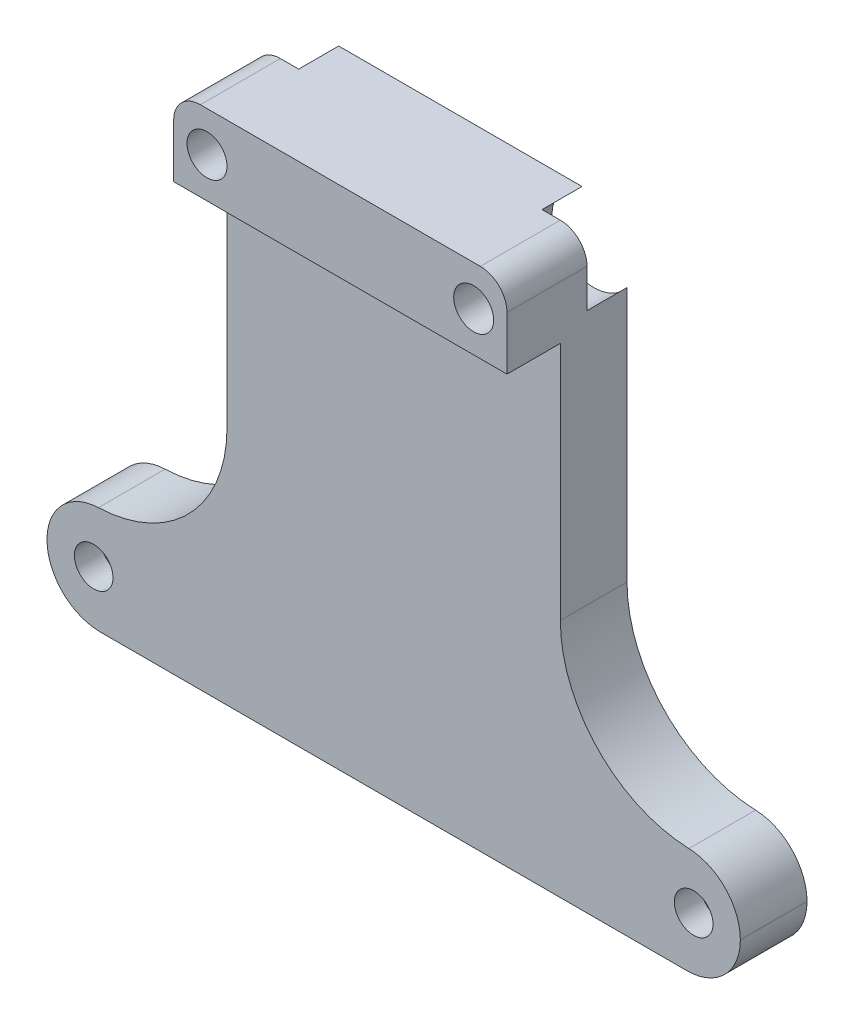
SolidWorks part; units mm, degrees
ref_plane "Спереди" through (0, 0, 0) normal (0, 0, 1) x (1, 0, 0)
ref_plane "Сверху" through (0, 0, 0) normal (0, 1, 0) x (1, 0, 0)
ref_plane "Справа" through (0, 0, 0) normal (1, 0, 0) x (0, 0, -1)
sketch "Эскиз1" plane through (0, 0, 0) normal (0, 0, 1) x (1, 0, 0)
  line L0 (-1000, 0) -> (49000, 0) construction
  line L1 (-26, -4) -> (26, -4)
  line L2 (-26, -4) -> (-26, 4)
  line L3 (-26, 4) -> (26, 4)
  line L4 (26, -4) -> (26, 4)
  line L5 (-26, -4) -> (26, 4) construction
  line L6 (-26, 4) -> (26, -4) construction
  circle A0 centre (-22.5, 0) radius 1.45
  circle A1 centre (22.5, 0) radius 1.45
  point P0 (0, 0)
  dimension "D2" = 2.9
  dimension "D1" = 8
  dimension "D3" = 45
  dimension "D4" = 22.5
  dimension "D5" = 52
extrude "Бобышка-Вытянуть1" add sketch "Эскиз1" along normal blind 5
sketch "Эскиз2" plane through (0, 0, 0) normal (0, 0, -1) x (-1, 0, 0)
  line L0 (-26, 4) -> (26, 4) construction
  line L1 (-12.5, 4) -> (12.5, 4)
  line L2 (-12.5, 4) -> (-12.5, 38)
  line L3 (-12.5, 38) -> (12.5, 38)
  line L4 (12.5, 4) -> (12.5, 38)
  line L5 (-12.5, 4) -> (12.5, 38) construction
  line L6 (-12.5, 38) -> (12.5, 4) construction
  line L7 (-1006.5256, 35) -> (48993.4744, 35) construction
  line L8 (0, -1000) -> (0, 49000) construction
  circle A0 centre (-10, 35) radius 1.5
  circle A1 centre (10, 35) radius 1.5
  point P4 (0, 21)
  dimension "D1" = 20
  dimension "D3" = 3
  dimension "D2" = 10
  dimension "D4" = 25
  dimension "D5" = 31
  dimension "D6" = 34
extrude "Бобышка-Вытянуть2" add sketch "Эскиз2" against normal blind 5
sketch "Эскиз3" plane through (0, 0, 5) normal (0, 0, -1) x (-1, 0, 0)
  line L0 (12.5, 4) -> (12.5, 38) construction
  line L1 (-12.5, 38) -> (12.5, 38)
  line L2 (-12.5, 38) -> (-12.5, 32)
  line L3 (-12.5, 32) -> (12.5, 32)
  line L4 (12.5, 38) -> (12.5, 32)
  line L5 (-12.5, 38) -> (12.5, 32) construction
  line L6 (-12.5, 32) -> (12.5, 38) construction
  circle A0 centre (10, 35) radius 1.5 construction
  circle A1 centre (-10, 35) radius 1.5 construction
  circle A2 centre (10, 35) radius 1.5
  circle A3 centre (-10, 35) radius 1.5
  point P4 (0, 35)
  dimension "D1" = 6
extrude "Бобышка-Вытянуть3" add sketch "Эскиз3" against normal blind 4
fillet "Скругление1" radius 10 2 edges at (12.5, 4, 2.5) (-12.5, 4, 2.5)
fillet "Скругление2" radius 4 4 edges at (-26, -4, 2.5) (-26, 4, 2.5) (26, -4, 2.5) (26, 4, 2.5)
fillet "Скругление3" radius 2 2 edges at (12.5, 38, 4.5) (-12.5, 38, 4.5)
sketch "Эскиз4" plane through (0, 0, 0) normal (0, 0, -1) x (-1, 0, 0)
  circle A0 centre (-10, 35) radius 3.125
  circle A1 centre (10, 35) radius 3.125
  circle A2 centre (-22.5, 0) radius 3.125
  circle A3 centre (22.5, 0) radius 3.125
  dimension "D1" = 6.25
extrude "Вырез-Вытянуть3" cut sketch "Эскиз4" against normal blind 3
